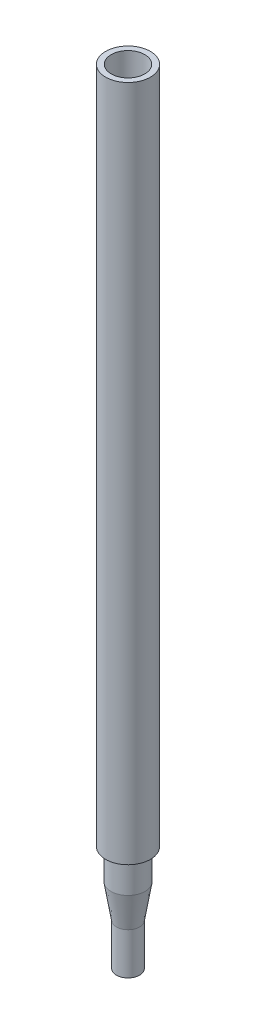
SolidWorks part; units mm, degrees
material "Acrylic (Medium-high impact)"
ref_plane "Front Plane" through (0, 0, 0) normal (0, 0, 1) x (1, 0, 0)
ref_plane "Top Plane" through (0, 0, 0) normal (0, 1, 0) x (1, 0, 0)
ref_plane "Right Plane" through (0, 0, 0) normal (1, 0, 0) x (0, 0, -1)
ref_axis "X-axis" through (-88.99, 0, 0) along (1, 0, 0)
ref_axis "Y-axis" through (0, 55, 0) along (0, -1, 0)
ref_axis "Z-axis" through (0, 0, -88.99) along (0, 0, 1)
sketch "Sketch1" plane through (0, 0, 0) normal (1, 0, 0) x (0, 0, -1)
  line L0 (0, 0) -> (0, 105) construction
  line L1 (-1.555, 0) -> (-1.555, 5.6)
  line L2 (-1.555, 5.6) -> (-2.29, 10.1029)
  line L3 (-2.29, 10.1029) -> (-2.29, 13.6729)
  line L4 (-2.29, 13.6729) -> (-3, 14.17)
  line L5 (-3, 14.17) -> (-3, 105)
  line L6 (-0.805, 0) -> (-0.805, 5.6608)
  line L7 (-0.805, 5.6608) -> (-1.54, 10.1637)
  line L8 (-1.54, 10.1637) -> (-1.54, 14.0633)
  line L9 (-1.54, 14.0633) -> (-2.25, 14.5604)
  line L10 (-2.25, 14.5604) -> (-2.25, 105)
  line L11 (-1.555, 0) -> (-0.805, 0)
  line L12 (-2.25, 105) -> (-3, 105)
  dimension "D1" = 105
  dimension "D2" = 90.83
  dimension "D3" = 125
  dimension "D4" = 3.11
  dimension "D5" = 3.57
  dimension "D6" = 5.6
  dimension "D7" = 6
  dimension "D8" = 4.58
  dimension "D9" = 0.75
revolve "Revolve1" add sketch "Sketch1" angle 360 about L0
